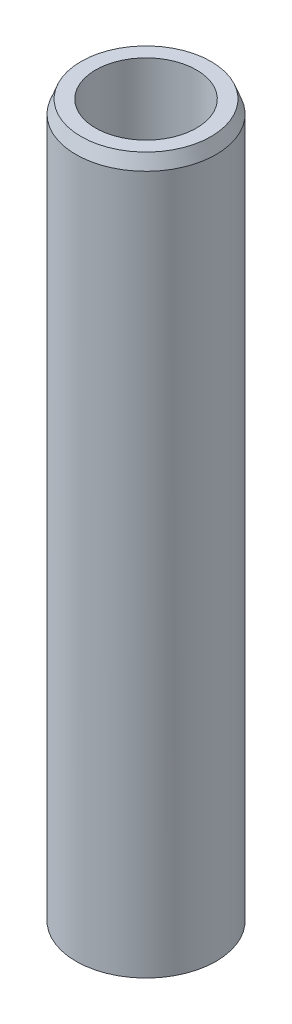
SolidWorks part; units mm, degrees
ref_plane "Front Plane" through (0, 0, 0) normal (0, 0, 1) x (1, 0, 0)
ref_plane "Top Plane" through (0, 0, 0) normal (0, 1, 0) x (1, 0, 0)
ref_plane "Right Plane" through (0, 0, 0) normal (1, 0, 0) x (0, 0, -1)
sketch "Sketch1" plane through (0, 0, 0) normal (0, 1, 0) x (1, 0, 0)
  circle A0 centre (0, 0) radius 20
  dimension "SHAFT_OD" = 40
extrude "Boss-Extrude1" add sketch "Sketch1" along normal blind 204.6326
sketch "Sketch2" plane through (0, 0, 0) normal (0, 1, 0) x (1, 0, 0)
  circle A0 centre (0, 0) radius 14.3952
  dimension "BORE_D" = 28.7904
extrude "Cut-Extrude1" cut sketch "Sketch2" along normal through all
chamfer "Chamfer1" distance 3.7411 angle 20.977 2 edges at (0, 204.6326, 20) (0, 0, 20) first distance on face at (0, 204.6326, 20) first distance on face at (0, 0, 14.3952)
